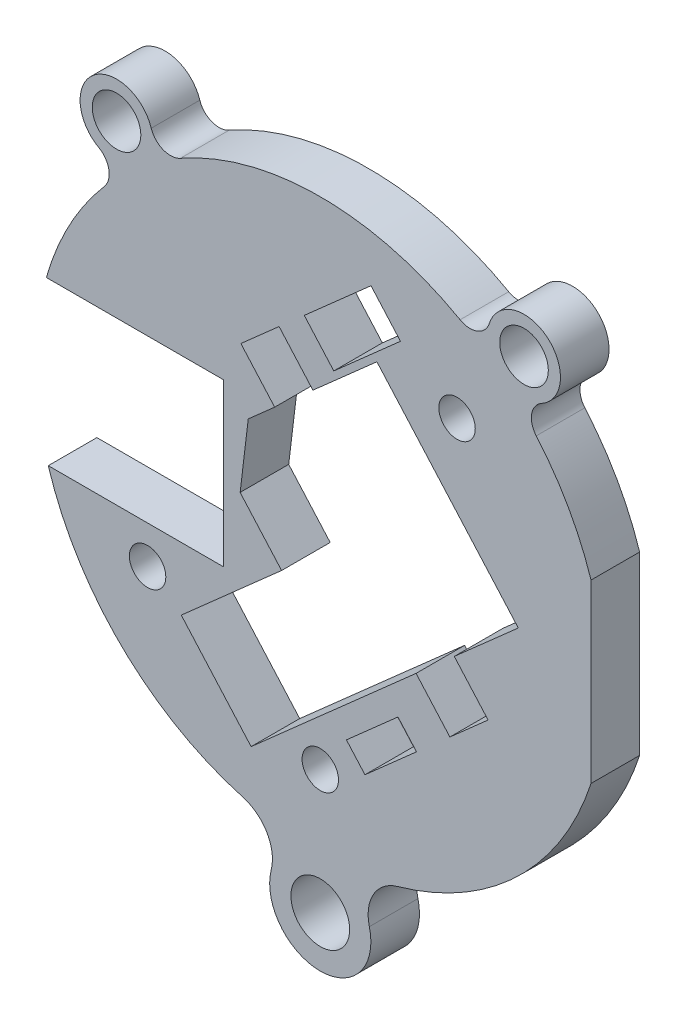
SolidWorks part; units mm, degrees
ref_plane "Front Plane" through (0, 0, 0) normal (0, 0, 1) x (1, 0, 0)
ref_plane "Top Plane" through (0, 0, 0) normal (0, 1, 0) x (1, 0, 0)
ref_plane "Right Plane" through (0, 0, 0) normal (1, 0, 0) x (0, 0, -1)
sketch "Sketch1" plane through (0, 0, 0) normal (0, 0, 1) x (1, 0, 0)
  line L0 (-21.141, 18.2245) -> (20.1141, 18.2245) construction
  line L1 (-4.8006, 1.8415) -> (-4.8006, -3.0861)
  line L2 (-4.8006, -3.0861) -> (-8.9662, -3.0861)
  line L3 (-8.9662, -3.0861) -> (-8.9662, -5.3514)
  line L4 (-8.9662, -5.3514) -> (-6.5786, -5.3514)
  line L5 (-4.9806, 7.3918) -> (-2.5835, 9.5123)
  line L6 (-2.5835, 9.5123) -> (-0.463, 7.1152)
  line L7 (-4.9806, 7.3918) -> (-2.8601, 4.9947)
  line L8 (3.2088, 10.3632) -> (-4.5153, 3.5306)
  line L9 (12.0777, 0.3371) -> (4.3536, -6.4955)
  line L10 (-4.5153, 3.5306) -> (-5.0276, -0.7207)
  line L11 (-5.0276, -0.7207) -> (0.0716, -6.4852)
  line L12 (0.0716, -6.4852) -> (4.3536, -6.4955)
  line L13 (-2.478, -3.6029) -> (7.6432, 5.3502) construction
  line L14 (3.2088, 10.3632) -> (12.0777, 0.3371)
  line L15 (3.2088, 10.3632) -> (11.8761, 18.0302)
  line L16 (-9.2588, -8.622) -> (-4.7522, -4.6355) construction
  line L17 (-9.2588, -8.622) -> (-5.994, -12.3128) construction
  line L18 (-4.7522, -4.6355) -> (-1.4874, -8.3263) construction
  line L19 (-5.994, -12.3128) -> (-1.4874, -8.3263) construction
  line L20 (12.0777, 0.3371) -> (20.228, 7.5468)
  line L21 (-6.5786, -5.3514) -> (-6.5786, -5.8039)
  line L22 (-6.5786, -5.8039) -> (-14.0208, -5.8039)
  line L23 (-14.0208, -5.8039) -> (-14.0208, 4.5593)
  line L24 (-14.0208, 4.5593) -> (-6.5786, 4.5593)
  line L25 (-6.5786, 4.5593) -> (-6.5786, 3.9924)
  line L26 (-6.5786, 3.9924) -> (-8.9662, 3.9924)
  line L27 (-8.9662, 3.9924) -> (-8.9662, 1.8415)
  line L28 (-8.9662, 1.8415) -> (-4.8006, 1.8415)
  line L29 (8.4059, -2.9109) -> (10.5264, -5.308)
  line L30 (10.5264, -5.308) -> (8.1292, -7.4285)
  line L31 (8.1292, -7.4285) -> (6.0088, -5.0313)
  line L32 (-4.7522, -4.6355) -> (-2.9639, -3.0536) construction
  line L33 (-1.4874, -8.3263) -> (0.5926, -6.4864) construction
  line L34 (-5.4555, -12.9216) -> (-0.9489, -8.9351)
  line L35 (-8.7203, -9.2308) -> (-4.2137, -5.2443)
  line L36 (-8.7203, -9.2308) -> (-5.4555, -12.9216)
  line L37 (-0.9489, -8.9351) -> (1.816, -6.4894)
  line L38 (-4.2137, -5.2443) -> (-2.4254, -3.6624)
  arc A0 (-15.2315, -0.5079) -> (3.302, 14.878) centre (0, 0) ccw construction
  circle A1 centre (0, 0) radius 21.59 construction
  circle A2 centre (0, 0) radius 21.59
  circle A3 centre (0, -18.415) radius 1.4224 construction
  circle A4 centre (0, 18.415) radius 1.4224 construction
  circle A5 centre (0, -18.415) radius 1.4224
  circle A6 centre (0, 18.415) radius 1.4224
  circle A7 centre (0, 0) radius 15.24
  dimension "D3" = 30.48
  dimension "D1" = 33.4645
  dimension "D2" = 20.0406
  dimension "D4" = 4.9276
  dimension "D5" = 2.7178
  dimension "D6" = 8.7122
  dimension "D7" = 7.8613
  dimension "D8" = 2.7178
  dimension "D9" = 3.2004
  dimension "D10" = 13.3858
  dimension "D11" = 3.1623
  dimension "D12" = 10.3124
  dimension "D13" = 8.6106
  dimension "D14" = 7.6962
  dimension "D15" = 6.0168
  dimension "D16" = 2.3876
  dimension "D17" = 4.9276
  dimension "D18" = 22.86
  dimension "D19" = 7.4422
  dimension "D20" = 5.0546
  dimension "D21" = 13.6652
  dimension "D22" = 29.2608
  dimension "D23" = 0.8128
extrude "Boss-Extrude1" add sketch "Sketch1" along normal blind 3.048 contours L15 A7 L20 L9 L29 L30 L31 L12 L33 L19 L17 L16 L32 L11 L1 L2 L3 L4 L21 L22 L23 L24 L25 L26 L27 L28 L10 L8 L7 L5 L6 | L28 L27 L26 L25 L24 L23 L22 L21 L4 L3 L2 L1 L11 L10 | A7 L15 A2 L20 A6 A5 region at (-6.8834, 2.2726, 0) region at (-10.1343, -0.6067, 0) region at (-13.5004, -8.3055, 0)
sketch "Sketch2" plane through (0, 0, 3.048) normal (0, 0, 1) x (1, 0, 0)
  line L0 (-5.0276, 2.3876) -> (-5.0276, -2.794)
  line L1 (-5.0276, 2.3876) -> (-10.4871, 2.3876)
  line L2 (-10.4871, 2.3876) -> (-10.4871, 3.8608)
  line L3 (-10.4871, 3.8608) -> (-7.085, 3.8608)
  line L4 (-7.085, 3.8608) -> (-7.085, 4.8768)
  line L5 (-7.085, 4.8768) -> (-14.4764, 4.8768)
  line L6 (-14.4764, 4.8768) -> (-14.4764, -5.2832)
  line L7 (-14.4764, -5.2832) -> (-7.085, -5.2832)
  line L8 (-7.085, -5.2832) -> (-7.085, -4.2672)
  line L9 (-7.085, -4.2672) -> (-10.4871, -4.2672)
  line L10 (-10.4871, -4.2672) -> (-10.4871, -2.794)
  line L11 (-10.4871, -2.794) -> (-5.0276, -2.794)
  line L12 (-5.0276, 2.3876) -> (-4.653, 2.3876)
  line L13 (-4.5153, 3.5306) -> (-5.0276, -0.7207) construction
  line L14 (-5.0276, -2.794) -> (-3.1935, -2.794)
  line L15 (-5.0276, -0.7207) -> (-2.4254, -3.6624) construction
  line L16 (-7.085, 3.8608) -> (-7.085, -4.2672)
  line L17 (-14.4764, 4.8768) -> (-21.032, 4.8768)
  line L18 (-14.4764, -5.2832) -> (-20.9336, -5.2832)
  arc A0 (11.8761, 18.0302) -> (20.228, 7.5468) centre (0, 0) ccw construction
  arc M2 (11.8761, 18.0302) -> (20.228, 7.5468) centre (0, 0) ccw
  dimension "D1" = 9.4488
  dimension "D2" = 7.3914
  dimension "D3" = 10.16
  dimension "D4" = 1.016
  dimension "D5" = 5.1816
  dimension "D6" = 5.4596
  dimension "D7" = 1.4732
  dimension "D8" = 1.143
extrude "Cut-Extrude3" cut sketch "Sketch2" against normal through all contours L10 L11 L0 L1 L2 L3 L4 L5 L6 L7 L8 L9 | L16 L3 L2 L1 | L16 L11 L10 L9 | L18 L6 L17 M2 region at (-11.0879, -0.2032, 3.048) region at (-8.7861, 3.1242, 3.048) region at (-8.7861, -3.5306, 3.048) region at (-17.9346, -0.1913, 3.048)
sketch "Sketch3" plane through (0, 0, 0) normal (0, 0, -1) x (-1, 0, 0)
  line L0 (-20.8712, -5.5245) -> (-16.9841, -5.5245)
  line L1 (-16.9841, -5.5245) -> (-20.8712, -5.5245) construction
  line L2 (-16.9841, -5.5245) -> (-16.9841, 4.6772)
  line L3 (-8.4059, -2.9109) -> (-20.228, 7.5468) construction
  line L4 (-16.9841, 5.5245) -> (-16.9841, -5.5245) construction
  line L5 (-16.9841, 4.6772) -> (-20.228, 7.5468)
  arc A0 (-20.228, 7.5468) -> (20.9336, -5.2832) centre (0, 0) ccw construction
  arc A1 (-20.228, 7.5468) -> (-20.8712, -5.5245) centre (0, 0) ccw
  arc A2 (-20.8712, -5.5245) -> (-20.8712, 5.5245) centre (0, 0) ccw construction
extrude "Cut-Extrude4" cut sketch "Sketch3" against normal through all
sketch "Sketch4" plane through (0, 0, 0) normal (0, 0, -1) x (-1, 0, 0)
  line L0 (-12.3201, -16.1591) -> (12.3201, 16.1591) construction
  line L1 (-13.8351, -15.0041) -> (10.8052, 17.3141)
  line L2 (-10.8052, -17.3141) -> (13.8351, 15.0041)
  line L3 (-16.1591, 12.3201) -> (16.1591, -12.3201) construction
  line L4 (-15.0041, 13.8351) -> (17.3141, -10.8052)
  line L5 (-17.3141, 10.8052) -> (15.0041, -13.8351)
  line L6 (-16.9841, 5.5245) -> (-16.9841, 4.6772)
  line L7 (-16.9841, 4.6772) -> (-12.4201, 0.64)
  line L8 (-8.4059, -2.9109) -> (-16.9841, 4.6772) construction
  line L9 (-12.4201, 0.64) -> (-3.5512, 10.6661)
  line L10 (0.463, 7.1152) -> (-11.8761, 18.0302) construction
  line L11 (-3.5512, 10.6661) -> (-8.9594, 15.4501)
  line L12 (5.0276, -0.7207) -> (2.4254, -3.6624) construction
  line L13 (0, 0) -> (2.7145, -20.1379) construction
  line L14 (1.8879, 0.2545) -> (4.6025, -19.8834)
  line L15 (-1.8879, -0.2545) -> (0.8266, -20.3924)
  line L16 (-16.1591, 12.3201) -> (12.3201, 16.1591) construction
  circle A0 centre (0, 0) radius 17.86
  arc A1 (-13.8351, -15.0041) -> (-10.8052, -17.3141) centre (-12.3201, -16.1591) ccw
  arc A2 (13.8351, 15.0041) -> (10.8052, 17.3141) centre (12.3201, 16.1591) ccw
  arc A3 (-15.0041, 13.8351) -> (-17.3141, 10.8052) centre (-16.1591, 12.3201) ccw
  arc A4 (15.0041, -13.8351) -> (17.3141, -10.8052) centre (16.1591, -12.3201) ccw
  circle A5 centre (12.3201, 16.1591) radius 1.1049
  circle A6 centre (16.1591, -12.3201) radius 1.1049
  circle A7 centre (-12.3201, -16.1591) radius 1.1049
  circle A8 centre (-16.1591, 12.3201) radius 1.1049
  arc A9 (1.8879, 0.2545) -> (-1.8879, -0.2545) centre (0, 0) ccw
  arc A10 (0.8266, -20.3924) -> (4.6025, -19.8834) centre (2.7145, -20.1379) ccw
  arc A11 (2.7145, -20.1379) -> (16.1591, -12.3201) centre (0, 0) ccw construction
  circle A12 centre (2.7145, -20.1379) radius 1.1049
  point P6 (0, 0)
  point P13 (0, 0)
  point P39 (1.3573, -10.0689)
  line M1 (-8.4059, -2.9109) -> (-16.9841, 4.6772)
  line M3 (-16.9841, -5.5245) -> (-20.8712, -5.5245)
  arc M4 (-20.8712, -5.5245) -> (20.9336, -5.2832) centre (0, 0) ccw
  line M5 (20.9336, -5.2832) -> (7.085, -5.2832)
  line M7 (7.085, 4.8768) -> (21.032, 4.8768)
  arc M8 (21.032, 4.8768) -> (-11.8761, 18.0302) centre (0, 0) ccw
  line M9 (-11.8761, 18.0302) -> (0.463, 7.1152)
  circle M24 centre (0, 18.415) radius 1.4224
  circle M25 centre (0, -18.415) radius 1.4224
  dimension "D1" = 3.81
  dimension "D2" = 3.81
  dimension "D3" = 13.97
extrude "Boss-Extrude2" add sketch "Sketch4" against normal up to vertex (3.048 mm away) contours A0 L4 L9 M9 | L4 A0 L5 L9 | L5 A0 L6 L9 M1 | L4 A3 L5 A0 A8 | A2 L1 A0 L2 A5 M8 | A0 M24 | A0 M25 | A0 L15 M25 | L15 A0 M25 | A10 M4 | A2 M8 region at (13.4131, 4.8762, 0) region at (10.9588, 8.3691, 0) region at (16.2523, 10.0852, 0) region at (0.2829, -17.4804, 0) region at (-2.9174, -21.6425, 0) region at (8.1323, 11.4955, 0) region at (-0.7535, -17.5272, 0) region at (-0.9598, -18.5708, 0) region at (-10.0849, 16.2525, 0) region at (0, 17.4932, 0) region at (-13.2407, 17.3665, 0) up to point (10.5264, -5.308, 3.048)
extrude "Cut-Extrude5" cut sketch "Sketch4<3>" against normal through all contours A4 L5 A0 L2 A1 M25 M4 | A4 A0 L4 M4 M5 | A1 L1 A0 M3 M4 | A7 | A6 | A5 | A2 L2 A0 M7 M8 | A2 A0 L1 M8 M9 M24 | L1 A1 L2 A0 A7 M4 | A10 A4 L5 A0 L14 M4 | A4 L4 A0 L5 A6 M4 | A12 region at (16.6582, -10.306, 0) region at (13.002, -14.0284, 0) region at (5.4053, -18.8788, 0) region at (-9.8123, -16.8747, 0) region at (-5.4955, 17.2518, 0) region at (-15.6105, -14.0703, 0) region at (-16.798, 10.0037, 0) region at (-18.1332, -7.9591, 0) region at (-12.3201, 16.1591, 0) region at (-16.1591, -12.3201, 0) region at (12.3201, -16.1591, 0) region at (-2.7145, -20.1379, 0)
sketch "Sketch4<3>" plane through (0, 0, 0) normal (0, 0, -1) x (-1, 0, 0) same geometry as "Sketch4"
sketch "Sketch5" plane through (0, 0, 3.048) normal (0, 0, 1) x (1, 0, 0)
  line L0 (4.3536, -6.4955) -> (-4.3384, -14.1843)
  line L1 (-4.3384, -14.1843) -> (-5.4555, -12.9216)
  line L2 (-8.7203, -9.2308) -> (-5.4555, -12.9216) construction
  line L3 (6.0088, -5.0313) -> (4.3536, -6.4955) construction
  line L4 (-5.4555, -12.9216) -> (1.816, -6.4894)
  line L5 (1.816, -6.4894) -> (4.3536, -6.4955)
extrude "Cut-Extrude10" cut sketch "Sketch5" against normal through all
sketch "Sketch6" plane through (0, 0, 3.048) normal (0, 0, 1) x (1, 0, 0)
  line L0 (17.3141, 10.8052) -> (15.2768, 9.2519) construction
  line L1 (15.0041, 13.8351) -> (12.9668, 12.2818) construction
  line L2 (17.3141, 10.8052) -> (15.2768, 9.2519)
  line L3 (15.0041, 13.8351) -> (12.9668, 12.2818)
  line L4 (17.5451, 10.5023) -> (15.472, 8.9216)
  line L5 (14.7731, 14.138) -> (12.7, 12.5574)
  line L23 (-4.9801, -19.8325) -> (-4.6378, -17.2935)
  line L24 (-0.1068, -17.9043) -> (-0.449, -20.4433)
  line L25 (-4.9801, -19.8325) -> (-4.6318, -17.2489)
  line L26 (-0.1008, -17.8597) -> (-0.449, -20.4433)
  line L29 (14.7731, 14.138) -> (12.7358, 12.5847) construction
  line L30 (17.5451, 10.5023) -> (15.5078, 8.9489) construction
  line L31 (-14.138, 14.7731) -> (-12.5847, 12.7358)
  line L32 (-8.9489, 15.5078) -> (-10.5023, 17.5451)
  line L33 (-14.138, 14.7731) -> (-12.5574, 12.7)
  line L34 (-8.9216, 15.472) -> (-10.5023, 17.5451)
  arc A0 (17.3141, 10.8052) -> (15.0041, 13.8351) centre (16.1591, 12.3201) ccw construction
  arc A1 (17.3141, 10.8052) -> (15.0041, 13.8351) centre (16.1591, 12.3201) ccw
  arc A2 (17.5451, 10.5023) -> (14.7731, 14.138) centre (16.1591, 12.3201) ccw
  arc A11 (-4.9801, -19.8325) -> (-0.449, -20.4433) centre (-2.7145, -20.1379) ccw
  arc A12 (-4.9801, -19.8325) -> (-0.449, -20.4433) centre (-2.7145, -20.1379) ccw
  circle A14 centre (0, 0) radius 17.86
  arc A15 (-10.5023, 17.5451) -> (-14.138, 14.7731) centre (-12.3201, 16.1591) ccw
  arc A16 (-10.5023, 17.5451) -> (-14.138, 14.7731) centre (-12.3201, 16.1591) ccw
  line M25 (-4.2602, -17.3444) -> (-4.6025, -19.8834)
  arc M26 (-4.6025, -19.8834) -> (-0.8266, -20.3924) centre (-2.7145, -20.1379) ccw
  line M27 (-0.8266, -20.3924) -> (-0.4844, -17.8534)
  arc M28 (-0.4844, -17.8534) -> (16.9841, -5.5245) centre (0, 0) ccw
  arc M30 (16.9841, 5.5245) -> (15.2768, 9.2519) centre (0, 0) ccw
  line M31 (15.2768, 9.2519) -> (17.3141, 10.8052)
  arc M32 (17.3141, 10.8052) -> (15.0041, 13.8351) centre (16.1591, 12.3201) ccw
  line M33 (15.0041, 13.8351) -> (12.9668, 12.2818)
  arc M34 (12.9668, 12.2818) -> (-9.2519, 15.2768) centre (0, 0) ccw
  line M35 (-9.2519, 15.2768) -> (-10.8052, 17.3141)
  arc M36 (-10.8052, 17.3141) -> (-13.8351, 15.0041) centre (-12.3201, 16.1591) ccw
  line M37 (-13.8351, 15.0041) -> (-12.2818, 12.9668)
  arc M38 (-12.2818, 12.9668) -> (-17.1812, 4.8768) centre (0, 0) ccw
  arc M42 (-17.0607, -5.2832) -> (-4.2602, -17.3444) centre (0, 0) ccw
  dimension "D1" = 0.381
  dimension "D2" = 0.381
  dimension "D3" = 0.381
extrude "Boss-Extrude3" add sketch "Sketch6" against normal up to vertex contours L34 A16 L33 M38 M37 M36 M35 M34 | L25 A12 L26 M28 M27 M26 M25 M42 | L4 A2 L5 M34 M33 M32 M31 M30 region at (17.7383, 13.5242, 3.048) region at (-9.1284, 15.4449, 3.048) region at (-0.1744, -17.8725, 3.048) up to point (8.4059, -2.9109, 0)
sketch "Sketch7" plane through (0, 0, 0) normal (0, 0, -1) x (-1, 0, 0)
  line L0 (7.085, 4.8768) -> (6.0563, 4.8768)
  line L1 (6.0563, 4.8768) -> (6.0563, -5.2832)
  line L2 (6.0563, -5.2832) -> (7.085, -5.2832)
  line L3 (5.0276, -0.7207) -> (7.085, -0.7207) construction
  line L4 (7.085, 4.8768) -> (7.085, -5.2832) construction
  line L5 (7.085, 4.8768) -> (7.085, -5.2832)
  point P11 (6.0563, -0.7207)
extrude "Cut-Extrude11" cut sketch "Sketch7" against normal through all
sketch "Sketch8" plane through (0, 0, 3.048) normal (0, 0, 1) x (1, 0, 0)
  circle A0 centre (0, 0) radius 17.86
  circle A1 centre (0, 0) radius 23.4976
extrude "Cut-Extrude12" cut sketch "Sketch8" against normal through all
sketch "Sketch9" plane through (0, 0, 3.048) normal (0, 0, 1) x (1, 0, 0)
  line L0 (0, 17.86) -> (-14.5094, 17.86) construction
  circle A0 centre (12.7793, 15.574) radius 1.524
  circle A1 centre (12.7793, 15.574) radius 2.286
  circle A2 centre (14.5094, 12.4672) radius 1.27
  circle A3 centre (9.3946, 16.6642) radius 1.27
  circle A4 centre (-12.7793, 15.574) radius 2.286
  circle A5 centre (-9.3946, 16.6642) radius 1.27
  circle A6 centre (-14.5094, 12.4672) radius 1.27
  circle A7 centre (0, -21.035) radius 1.8415
  circle A8 centre (0, -21.035) radius 3.175
  circle A9 centre (5.5404, -19.6332) radius 2.54
  circle A10 centre (-5.5404, -19.6332) radius 2.54
  circle A11 centre (-12.7793, 15.574) radius 1.524
  circle A12 centre (0, 0) radius 17.86
  circle A13 centre (0, 0) radius 17.86
  arc A14 (16.9841, 5.5245) -> (-17.1812, 4.8768) centre (0, 0) ccw construction
  arc M17 (16.9841, 5.5245) -> (-17.1812, 4.8768) centre (0, 0) ccw
  arc M21 (-17.0607, -5.2832) -> (16.9841, -5.5245) centre (0, 0) ccw
  dimension "D1" = 3.048
  dimension "D2" = 4.572
  dimension "D3" = 2.54
  dimension "D4" = 2.54
  dimension "D5" = 3.683
  dimension "D6" = 6.35
  dimension "D7" = 5.08
extrude "Boss-Extrude4" add sketch "Sketch9" against normal up to vertex contours A2 A1 M17 | A1 A0 | A3 A1 M17 | A6 A4 M17 | A4 A11 | A5 A4 M17 | A8 A7 | A10 A8 M21 | A9 A8 M21 region at (14.6944, 14.4484, 3.048) region at (10.1667, 15.1037, 3.048) region at (12.8282, 12.9198, 3.048) region at (-10.1667, 15.1037, 3.048) region at (-10.5849, 15.9187, 3.048) region at (-12.8282, 12.9198, 3.048) region at (2.6103, -18.2487, 3.048) region at (3.0615, -20.6537, 3.048) region at (-2.6103, -18.2487, 3.048) up to point (-0.463, 7.1152, 0)
sketch "Sketch10" plane through (0, 0, 3.048) normal (0, 0, 1) x (1, 0, 0)
  circle A0 centre (-10.8325, -7.6454) radius 1.143
  circle A1 centre (0, -13.2588) radius 1.143
  circle A2 centre (8.579, 10.1092) radius 1.143
  dimension "D1" = 2.286
extrude "Cut-Extrude13" cut sketch "Sketch10" against normal through all
sketch "Sketch11" plane through (0, 0, 3.048) normal (0, 0, 1) x (1, 0, 0)
  line L0 (-1.0044, 10.9091) -> (0.8468, 8.8164)
  line L1 (0.8468, 8.8164) -> (5.0322, 12.5188)
  line L2 (5.0322, 12.5188) -> (3.181, 14.6115)
  line L3 (3.181, 14.6115) -> (-1.0044, 10.9091)
  line L4 (-4.9806, 7.3918) -> (-2.5835, 9.5123) construction
  line L5 (-2.5835, 9.5123) -> (-0.463, 7.1152) construction
  line L6 (6.0365, -9.2797) -> (2.8023, -12.1406)
  line L7 (2.8023, -12.1406) -> (1.6411, -10.8279)
  line L8 (1.6411, -10.8279) -> (4.8753, -7.967)
  line L9 (4.8753, -7.967) -> (6.0365, -9.2797)
  line L10 (10.5264, -5.308) -> (8.1292, -7.4285) construction
  line L11 (8.1292, -7.4285) -> (6.0088, -5.0313) construction
  point P6 (-1.5232, 8.3137)
  dimension "D1" = 2.794
  dimension "D2" = 2.1082
  dimension "D3" = 5.588
  dimension "D4" = 1.7526
  dimension "D5" = 4.318
  dimension "D6" = 2.794
extrude "Cut-Extrude14" cut sketch "Sketch11" against normal through all
sketch "Sketch13" plane through (0, 0, 3.048) normal (0, 0, 1) x (1, 0, 0)
  line B0 (-6.0563, 4.8768) -> (-17.1812, 4.8768)
  line B1 (-6.0563, 4.8768) -> (-6.0563, -5.2832)
  line B2 (-17.0607, -5.2832) -> (-6.0563, -5.2832)
  line B3 (-8.7203, -9.2308) -> (-2.4254, -3.6624)
  line B4 (-8.7203, -9.2308) -> (-4.3384, -14.1843)
  line B5 (6.0088, -5.0313) -> (-4.3384, -14.1843)
  line B6 (1.6411, -10.8279) -> (2.8023, -12.1406)
  line B7 (4.8753, -7.967) -> (1.6411, -10.8279)
  line B8 (2.8023, -12.1406) -> (6.0365, -9.2797)
  line B9 (6.0365, -9.2797) -> (4.8753, -7.967)
  line B10 (8.1292, -7.4285) -> (6.0088, -5.0313)
  line B11 (10.5264, -5.308) -> (8.1292, -7.4285)
  line B12 (8.4059, -2.9109) -> (10.5264, -5.308)
  line B13 (8.4059, -2.9109) -> (12.4201, 0.64)
  line B14 (12.4201, 0.64) -> (3.5512, 10.6661)
  line B15 (-0.463, 7.1152) -> (3.5512, 10.6661)
  line B16 (-2.5835, 9.5123) -> (-0.463, 7.1152)
  line B17 (-4.9806, 7.3918) -> (-2.5835, 9.5123)
  line B18 (-4.9806, 7.3918) -> (-2.8601, 4.9947)
  line B19 (-2.8601, 4.9947) -> (-4.5153, 3.5306)
  line B20 (-4.5153, 3.5306) -> (-5.0276, -0.7207)
  line B21 (-5.0276, -0.7207) -> (-2.4254, -3.6624)
  line B22 (-1.0044, 10.9091) -> (0.8468, 8.8164)
  line B23 (3.181, 14.6115) -> (-1.0044, 10.9091)
  line B24 (5.0322, 12.5188) -> (3.181, 14.6115)
  line B25 (0.8468, 8.8164) -> (5.0322, 12.5188)
  line B26 (16.9841, -5.5245) -> (16.9841, 5.5245)
  circle B27 centre (-10.8325, -7.6454) radius 1.143
  circle B28 centre (0, -13.2588) radius 1.143
  circle B29 centre (8.579, 10.1092) radius 1.143
sketch_block_instance "Block1-1"
sketch_block "Block1"
